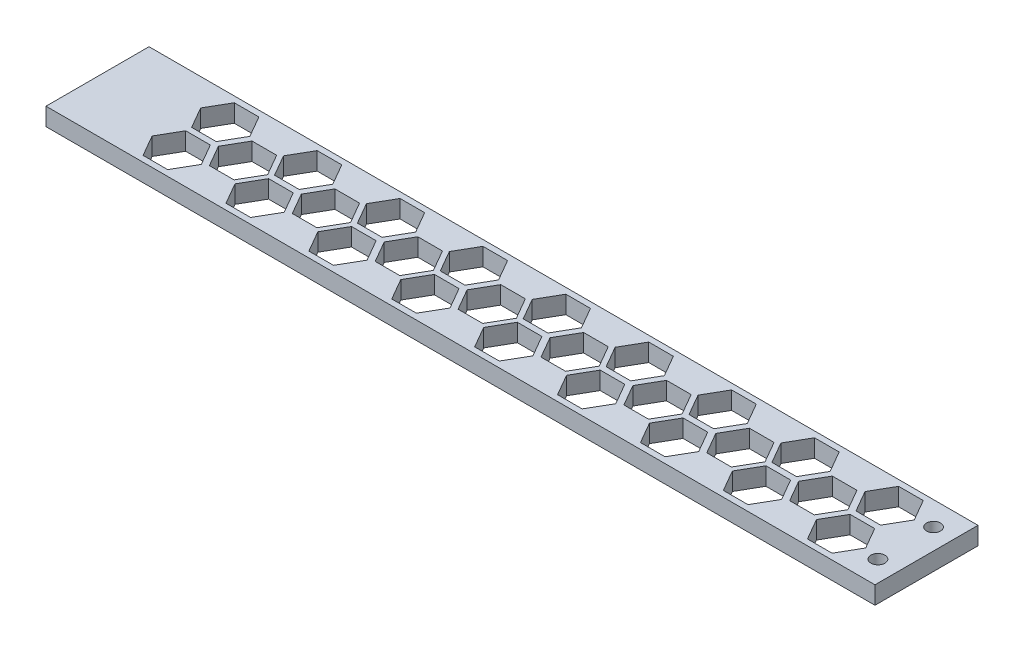
SolidWorks part; units mm, degrees
ref_plane "Front Plane" through (0, 0, 0) normal (0, 0, 1) x (1, 0, 0)
ref_plane "Top Plane" through (0, 0, 0) normal (0, 1, 0) x (1, 0, 0)
ref_plane "Right Plane" through (0, 0, 0) normal (1, 0, 0) x (0, 0, -1)
sketch "Sketch1" plane through (0, 0, 0) normal (0, 1, 0) x (1, 0, 0)
  line L1 (-88.9, 11.049) -> (88.9, 11.049)
  line L2 (-88.9, 11.049) -> (-88.9, -11.049)
  line L3 (-88.9, -11.049) -> (88.9, -11.049)
  line L4 (88.9, 11.049) -> (88.9, -11.049)
  line L5 (-88.9, 11.049) -> (88.9, -11.049) construction
  line L6 (-88.9, -11.049) -> (88.9, 11.049) construction
  circle A0 centre (84.455, 5.969) radius 1.5
  circle A1 centre (84.455, -5.969) radius 1.5
  point P0 (0, 0)
  dimension "D3" = 3
  dimension "D1" = 22.098
  dimension "D2" = 177.8
  dimension "D4" = 4.445
  dimension "D5" = 5.08
  dimension "D6" = 5.08
extrude "Boss-Extrude1" add sketch "Sketch1" along normal blind 3.81
sketch "Sketch2" plane through (0, 3.81, 0) normal (0, 1, 0) x (1, 0, 0)
  line L11 (-88.9, -11.049) -> (88.9, -11.049) construction
  line L12 (78.4281, -9.779) -> (81.0677, -5.207)
  line L13 (81.0677, -5.207) -> (78.4281, -0.635)
  line L14 (78.4281, -0.635) -> (73.1488, -0.635)
  line L15 (73.1488, -0.635) -> (70.5092, -5.207)
  line L16 (70.5092, -5.207) -> (73.1488, -9.779)
  line L17 (73.1488, -9.779) -> (78.4281, -9.779)
  line L18 (78.4281, 0.635) -> (81.0677, 5.207)
  line L19 (81.0677, 5.207) -> (78.4281, 9.779)
  line L20 (78.4281, 9.779) -> (73.1488, 9.779)
  line L21 (73.1488, 9.779) -> (70.5092, 5.207)
  line L22 (70.5092, 5.207) -> (73.1488, 0.635)
  line L23 (73.1488, 0.635) -> (78.4281, 0.635)
  line L25 (88.9, 11.049) -> (-88.9, 11.049) construction
  line L26 (60.3905, -9.779) -> (63.0302, -5.207)
  line L27 (63.0302, -5.207) -> (60.3905, -0.635)
  line L28 (60.3905, -0.635) -> (55.1112, -0.635)
  line L29 (55.1112, -0.635) -> (52.4716, -5.207)
  line L30 (52.4716, -5.207) -> (55.1112, -9.779)
  line L31 (55.1112, -9.779) -> (60.3905, -9.779)
  line L32 (60.3905, 0.635) -> (63.0302, 5.207)
  line L33 (63.0302, 5.207) -> (60.3905, 9.779)
  line L34 (60.3905, 9.779) -> (55.1112, 9.779)
  line L35 (55.1112, 9.779) -> (52.4716, 5.207)
  line L36 (52.4716, 5.207) -> (55.1112, 0.635)
  line L37 (55.1112, 0.635) -> (60.3905, 0.635)
  line L38 (51.6293, -4.572) -> (54.2689, 0)
  line L39 (69.4093, -4.572) -> (72.0489, 0)
  line L40 (72.0489, 0) -> (69.4093, 4.572)
  line L41 (69.4093, 4.572) -> (64.13, 4.572)
  line L42 (64.13, 4.572) -> (61.4904, 0)
  line L43 (61.4904, 0) -> (64.13, -4.572)
  line L44 (64.13, -4.572) -> (69.4093, -4.572)
  line L45 (54.2689, 0) -> (51.6293, 4.572)
  line L46 (51.6293, 4.572) -> (46.35, 4.572)
  line L47 (46.35, 4.572) -> (43.7104, 0)
  line L48 (43.7104, 0) -> (46.35, -4.572)
  line L49 (46.35, -4.572) -> (51.6293, -4.572)
  line L50 (42.6105, -9.779) -> (45.2502, -5.207)
  line L51 (45.2502, -5.207) -> (42.6105, -0.635)
  line L52 (42.6105, -0.635) -> (37.3312, -0.635)
  line L53 (37.3312, -0.635) -> (34.6916, -5.207)
  line L54 (34.6916, -5.207) -> (37.3312, -9.779)
  line L55 (37.3312, -9.779) -> (42.6105, -9.779)
  line L56 (42.6105, 0.635) -> (45.2502, 5.207)
  line L57 (45.2502, 5.207) -> (42.6105, 9.779)
  line L58 (42.6105, 9.779) -> (37.3312, 9.779)
  line L59 (37.3312, 9.779) -> (34.6916, 5.207)
  line L60 (34.6916, 5.207) -> (37.3312, 0.635)
  line L61 (37.3312, 0.635) -> (42.6105, 0.635)
  line L62 (33.8493, -4.572) -> (36.4889, 0)
  line L63 (36.4889, 0) -> (33.8493, 4.572)
  line L64 (33.8493, 4.572) -> (28.57, 4.572)
  line L65 (28.57, 4.572) -> (25.9304, 0)
  line L66 (25.9304, 0) -> (28.57, -4.572)
  line L67 (28.57, -4.572) -> (33.8493, -4.572)
  line L68 (24.8305, -9.779) -> (27.4702, -5.207)
  line L69 (27.4702, -5.207) -> (24.8305, -0.635)
  line L70 (24.8305, -0.635) -> (19.5512, -0.635)
  line L71 (19.5512, -0.635) -> (16.9116, -5.207)
  line L72 (16.9116, -5.207) -> (19.5512, -9.779)
  line L73 (19.5512, -9.779) -> (24.8305, -9.779)
  line L74 (24.8305, 0.635) -> (27.4702, 5.207)
  line L75 (27.4702, 5.207) -> (24.8305, 9.779)
  line L76 (24.8305, 9.779) -> (19.5512, 9.779)
  line L77 (19.5512, 9.779) -> (16.9116, 5.207)
  line L78 (16.9116, 5.207) -> (19.5512, 0.635)
  line L79 (19.5512, 0.635) -> (24.8305, 0.635)
  line L80 (16.0693, -4.572) -> (18.7089, 0)
  line L81 (18.7089, 0) -> (16.0693, 4.572)
  line L82 (16.0693, 4.572) -> (10.79, 4.572)
  line L83 (10.79, 4.572) -> (8.1504, 0)
  line L84 (8.1504, 0) -> (10.79, -4.572)
  line L85 (10.79, -4.572) -> (16.0693, -4.572)
  line L86 (7.0505, -9.779) -> (9.6902, -5.207)
  line L87 (9.6902, -5.207) -> (7.0505, -0.635)
  line L88 (7.0505, -0.635) -> (1.7712, -0.635)
  line L89 (1.7712, -0.635) -> (-0.8684, -5.207)
  line L90 (-0.8684, -5.207) -> (1.7712, -9.779)
  line L91 (1.7712, -9.779) -> (7.0505, -9.779)
  line L92 (7.0505, 0.635) -> (9.6902, 5.207)
  line L93 (9.6902, 5.207) -> (7.0505, 9.779)
  line L94 (7.0505, 9.779) -> (1.7712, 9.779)
  line L95 (1.7712, 9.779) -> (-0.8684, 5.207)
  line L96 (-0.8684, 5.207) -> (1.7712, 0.635)
  line L97 (1.7712, 0.635) -> (7.0505, 0.635)
  line L98 (-1.7107, -4.572) -> (0.9289, 0)
  line L99 (0.9289, 0) -> (-1.7107, 4.572)
  line L100 (-1.7107, 4.572) -> (-6.99, 4.572)
  line L101 (-6.99, 4.572) -> (-9.6296, 0)
  line L102 (-9.6296, 0) -> (-6.99, -4.572)
  line L103 (-6.99, -4.572) -> (-1.7107, -4.572)
  line L104 (-10.7295, -9.779) -> (-8.0898, -5.207)
  line L105 (-8.0898, -5.207) -> (-10.7295, -0.635)
  line L106 (-10.7295, -0.635) -> (-16.0088, -0.635)
  line L107 (-16.0088, -0.635) -> (-18.6484, -5.207)
  line L108 (-18.6484, -5.207) -> (-16.0088, -9.779)
  line L109 (-16.0088, -9.779) -> (-10.7295, -9.779)
  line L110 (-10.7295, 0.635) -> (-8.0898, 5.207)
  line L111 (-8.0898, 5.207) -> (-10.7295, 9.779)
  line L112 (-10.7295, 9.779) -> (-16.0088, 9.779)
  line L113 (-16.0088, 9.779) -> (-18.6484, 5.207)
  line L114 (-18.6484, 5.207) -> (-16.0088, 0.635)
  line L115 (-16.0088, 0.635) -> (-10.7295, 0.635)
  line L116 (-19.4907, -4.572) -> (-16.8511, 0)
  line L117 (-16.8511, 0) -> (-19.4907, 4.572)
  line L118 (-19.4907, 4.572) -> (-24.77, 4.572)
  line L119 (-24.77, 4.572) -> (-27.4096, 0)
  line L120 (-27.4096, 0) -> (-24.77, -4.572)
  line L121 (-24.77, -4.572) -> (-19.4907, -4.572)
  line L122 (-28.5095, -9.779) -> (-25.8698, -5.207)
  line L123 (-25.8698, -5.207) -> (-28.5095, -0.635)
  line L124 (-28.5095, -0.635) -> (-33.7888, -0.635)
  line L125 (-33.7888, -0.635) -> (-36.4284, -5.207)
  line L126 (-36.4284, -5.207) -> (-33.7888, -9.779)
  line L127 (-33.7888, -9.779) -> (-28.5095, -9.779)
  line L128 (-28.5095, 0.635) -> (-25.8698, 5.207)
  line L129 (-25.8698, 5.207) -> (-28.5095, 9.779)
  line L130 (-28.5095, 9.779) -> (-33.7888, 9.779)
  line L131 (-33.7888, 9.779) -> (-36.4284, 5.207)
  line L132 (-36.4284, 5.207) -> (-33.7888, 0.635)
  line L133 (-33.7888, 0.635) -> (-28.5095, 0.635)
  line L134 (-37.2707, -4.572) -> (-34.6311, 0)
  line L135 (-34.6311, 0) -> (-37.2707, 4.572)
  line L136 (-37.2707, 4.572) -> (-42.55, 4.572)
  line L137 (-42.55, 4.572) -> (-45.1896, 0)
  line L138 (-45.1896, 0) -> (-42.55, -4.572)
  line L139 (-42.55, -4.572) -> (-37.2707, -4.572)
  line L140 (-46.2895, -9.779) -> (-43.6498, -5.207)
  line L141 (-43.6498, -5.207) -> (-46.2895, -0.635)
  line L142 (-46.2895, -0.635) -> (-51.5688, -0.635)
  line L143 (-51.5688, -0.635) -> (-54.2084, -5.207)
  line L144 (-54.2084, -5.207) -> (-51.5688, -9.779)
  line L145 (-51.5688, -9.779) -> (-46.2895, -9.779)
  line L146 (-46.2895, 0.635) -> (-43.6498, 5.207)
  line L147 (-43.6498, 5.207) -> (-46.2895, 9.779)
  line L148 (-46.2895, 9.779) -> (-51.5688, 9.779)
  line L149 (-51.5688, 9.779) -> (-54.2084, 5.207)
  line L150 (-54.2084, 5.207) -> (-51.5688, 0.635)
  line L151 (-51.5688, 0.635) -> (-46.2895, 0.635)
  line L152 (-55.0507, -4.572) -> (-52.4111, 0)
  line L153 (-52.4111, 0) -> (-55.0507, 4.572)
  line L154 (-55.0507, 4.572) -> (-60.33, 4.572)
  line L155 (-60.33, 4.572) -> (-62.9696, 0)
  line L156 (-62.9696, 0) -> (-60.33, -4.572)
  line L157 (-60.33, -4.572) -> (-55.0507, -4.572)
  line L158 (-64.0695, -9.779) -> (-61.4298, -5.207)
  line L159 (-61.4298, -5.207) -> (-64.0695, -0.635)
  line L160 (-64.0695, -0.635) -> (-69.3488, -0.635)
  line L161 (-69.3488, -0.635) -> (-71.9884, -5.207)
  line L162 (-71.9884, -5.207) -> (-69.3488, -9.779)
  line L163 (-69.3488, -9.779) -> (-64.0695, -9.779)
  line L164 (-64.0695, 0.635) -> (-61.4298, 5.207)
  line L165 (-61.4298, 5.207) -> (-64.0695, 9.779)
  line L166 (-64.0695, 9.779) -> (-69.3488, 9.779)
  line L167 (-69.3488, 9.779) -> (-71.9884, 5.207)
  line L168 (-71.9884, 5.207) -> (-69.3488, 0.635)
  line L169 (-69.3488, 0.635) -> (-64.0695, 0.635)
  circle A0 centre (75.7884, -5.207) radius 4.572 construction
  circle A1 centre (66.7697, 0) radius 4.572 construction
  dimension "D1" = 9.144
  dimension "D6" = 9.144
  dimension "D2" = 1.27
  dimension "D4" = 1.27
  dimension "D5" = 1.27
  dimension "D7" = 1.27
  dimension "D9" = 1.27
  dimension "D3" = 2
  dimension "D8" = 2
extrude "Cut-Extrude1" cut sketch "Sketch2" against normal up to next (3.81 mm away)
